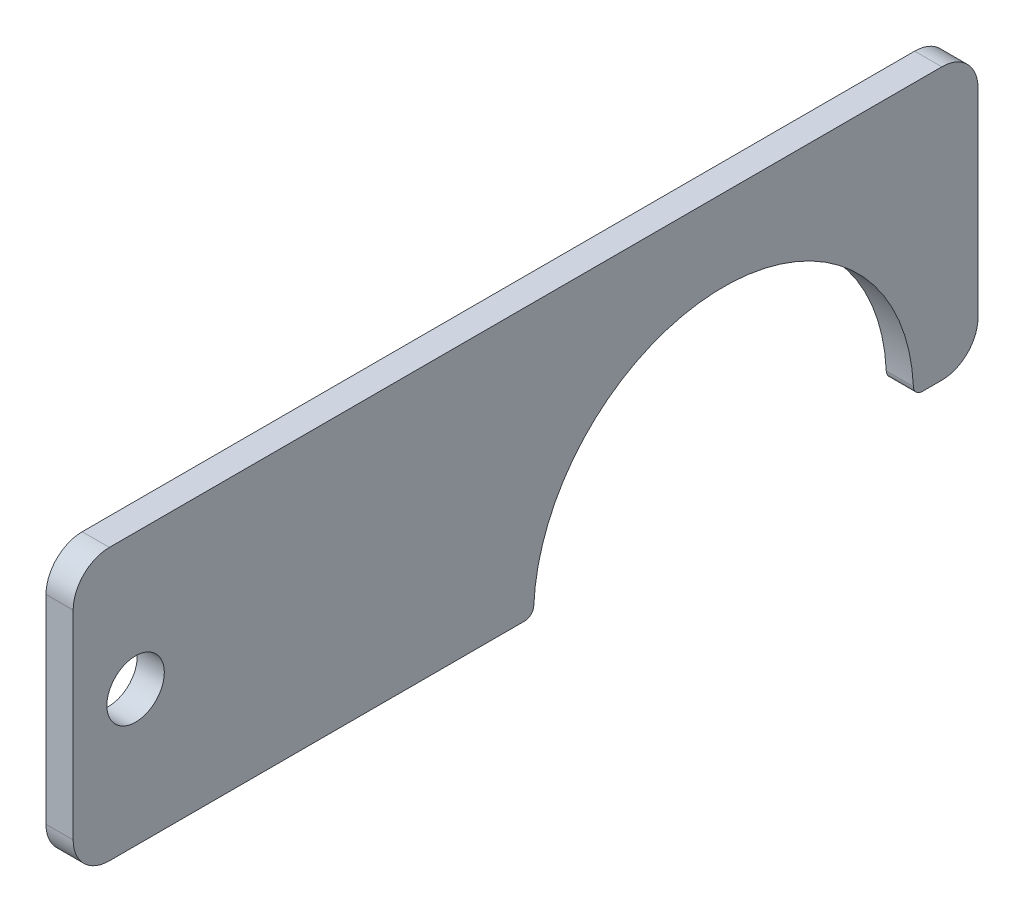
SolidWorks part; units mm, degrees
ref_plane "Front Plane" through (0, 0, 0) normal (0, 0, 1) x (1, 0, 0)
ref_plane "Top Plane" through (0, 0, 0) normal (0, 1, 0) x (1, 0, 0)
ref_plane "Right Plane" through (0, 0, 0) normal (1, 0, 0) x (0, 0, -1)
sketch "Sketch1" plane through (0, 0, 0) normal (1, 0, 0) x (0, 0, -1)
  line L0 (0, 0) -> (100, 0)
  line L3 (50.8832, -30) -> (0, -30)
  line L4 (0, -30) -> (0, 0)
  line L5 (100, 0) -> (100, -30)
  line L6 (100, -30) -> (92.8832, -30)
  line L7 (92.8832, -30) -> (50.8832, -30) construction
  arc A0 (50.8832, -30) -> (92.8832, -30) centre (71.8832, -30) cw
  point P7 (0, 0)
  point P8 (0, 0)
  dimension "D3" = 21
  dimension "D1" = 30
  dimension "D2" = 100
  dimension "D4" = 30
extrude "Boss-Extrude1" add sketch "Sketch1" along normal blind 3
sketch "Sketch2" plane through (3, 0, 0) normal (1, 0, 0) x (0, 0, -1)
  line L0 (0, 0) -> (0, -30) construction
  circle A0 centre (6.9009, -15) radius 3.175
  point P4 (0, -15)
  dimension "D1" = 6.35
extrude "Cut-Extrude1" cut sketch "Sketch2" against normal through all
fillet "Fillet1" radius 4 4 edges at (1.5, -30, 0) (1.5, 0, 0) (1.5, -30, -100) (1.5, 0, -100)
fillet "Fillet2" radius 1 2 edges at (1.5, -30, -50.8832) (1.5, -30, -92.8832)
